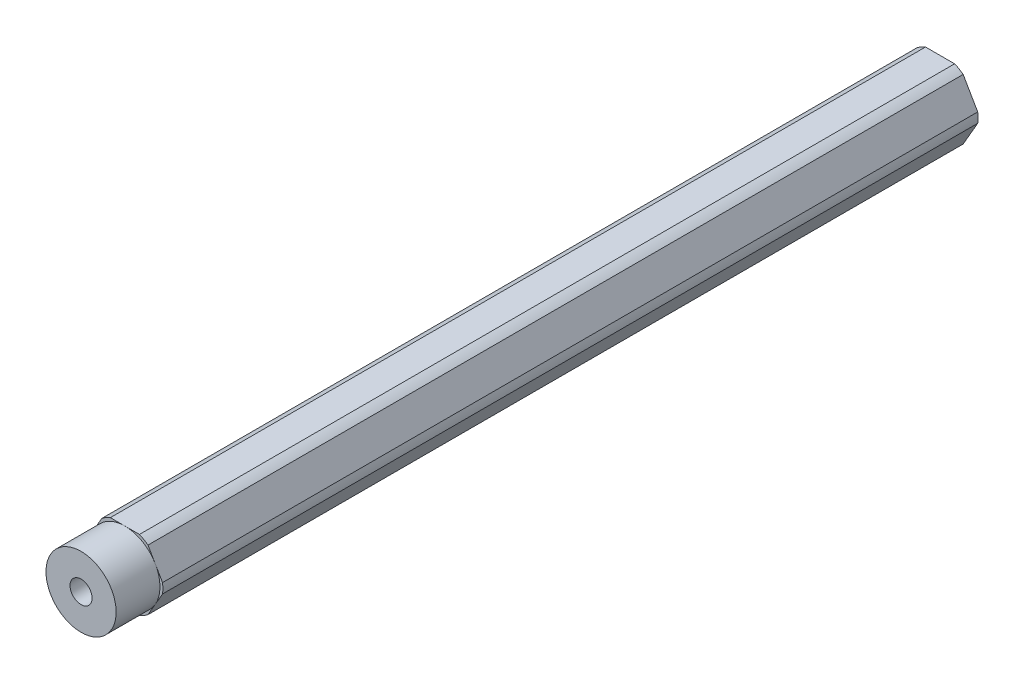
SolidWorks part; units mm, degrees
material "6061-T6 (SS)"
ref_plane "Front Plane" through (0, 0, 0) normal (0, 0, 1) x (1, 0, 0)
ref_plane "Top Plane" through (0, 0, 0) normal (0, 1, 0) x (1, 0, 0)
ref_plane "Right Plane" through (0, 0, 0) normal (1, 0, 0) x (0, 0, -1)
sketch "Sketch1" plane through (0, 0, 0) normal (0, 0, 1) x (1, 0, 0)
  line L1 (3.6662, 6.35) -> (-3.6662, 6.35)
  line L2 (-3.6662, 6.35) -> (-7.3323, 0)
  line L3 (-7.3323, 0) -> (-3.6662, -6.35)
  line L4 (-3.6662, -6.35) -> (3.6662, -6.35)
  line L5 (3.6662, -6.35) -> (7.3323, 0)
  line L6 (7.3323, 0) -> (3.6662, 6.35)
  circle A0 centre (0, 0) radius 6.35 construction
  circle A1 centre (0, 0) radius 2
  circle A2 centre (0, 0) radius 6.875
  point P1 (0, 6.35)
  dimension "D2" = 13.75
  dimension "D3" = 4
  dimension "D1" = 12.7
extrude "Boss-Extrude1" add sketch "Sketch1" along normal mid plane 147.5867 contours L6 A2 L1 L2 L3 L4 L5 A1 region at (3.3439, 5.7918, 0)
sketch "Sketch4" plane through (0, 0, 73.7934) normal (0, 0, 1) x (1, 0, 0)
  circle A0 centre (0, 0) radius 6.35
  circle A1 centre (0, 0) radius 2 construction
  circle A2 centre (0, 0) radius 2
  dimension "D1" = 12.7
extrude "Boss-Extrude2" add sketch "Sketch4" along normal blind 7.9375
equation "\"D2@Sketch1\"=13.75mm"
equation "\"D3@Sketch1\"=4mm"
